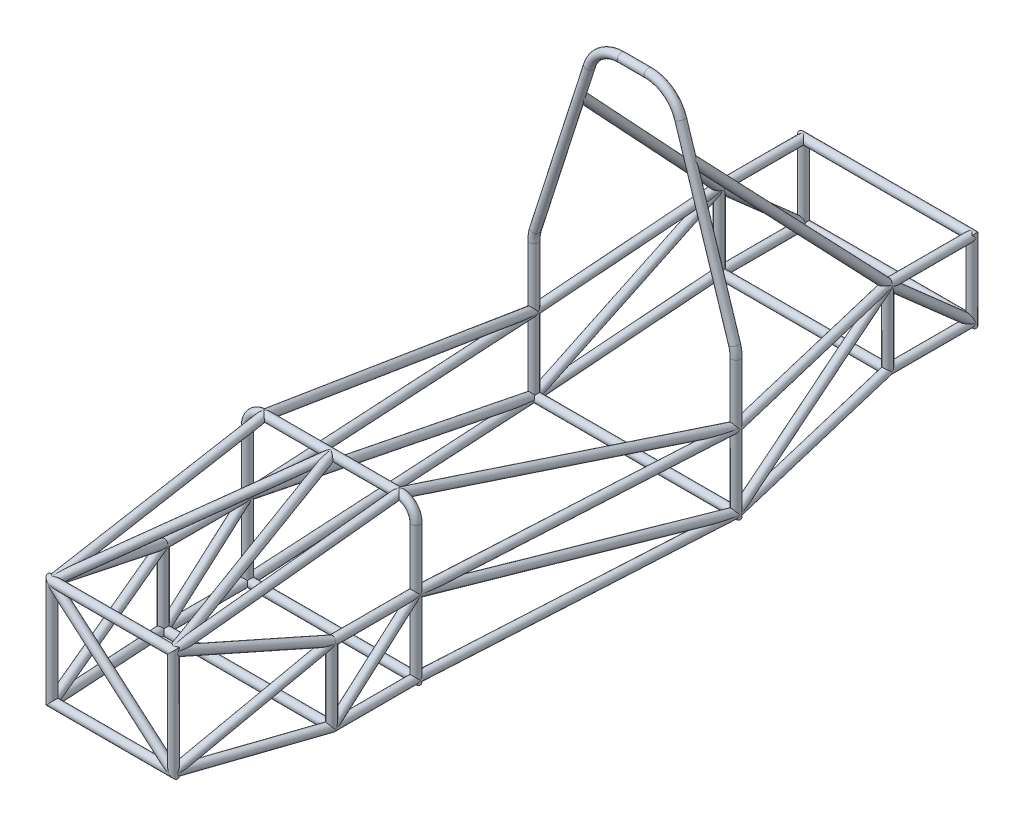
SolidWorks part; units mm, degrees
ref_plane "Front Plane" through (0, 0, 0) normal (0, 0, 1) x (1, 0, 0)
ref_plane "Top Plane" through (0, 0, 0) normal (0, 1, 0) x (1, 0, 0)
ref_plane "Right Plane" through (0, 0, 0) normal (1, 0, 0) x (0, 0, -1)
sketch "Sketch1" plane through (0, 0, 0) normal (0, 0, 1) x (1, 0, 0)
  line L0 (0, 0) -> (0, 400)
  line L1 (4.7576, 430.4776) -> (164.7576, 930.4776)
  line L2 (260, 1000) -> (340, 1000)
  line L3 (435.2424, 930.4776) -> (595.2424, 430.4776)
  line L4 (600, 400) -> (600, 0)
  line L5 (600, 0) -> (0, 0)
  line L6 (300, -975.9464) -> (300, 49024.0536) construction
  arc A0 (595.2424, 430.4776) -> (600, 400) centre (500, 400) cw
  arc A1 (0, 400) -> (4.7576, 430.4776) centre (100, 400) cw
  arc A2 (340, 1000) -> (435.2424, 930.4776) centre (340, 900) cw
  arc A3 (164.7576, 930.4776) -> (260, 1000) centre (260, 900) cw
  dimension "D2" = 100
  dimension "D3" = 100
  dimension "D1" = 600
  dimension "D4" = 300
  dimension "D5" = 400
  dimension "D6" = 80
  dimension "D7" = 1000
sketch "Sketch3" plane through (0, 0, 0) normal (0, 1, 0) x (1, 0, 0)
  line L0 (300, -1107.0637) -> (300, 51069.4933) construction
  dimension "D1" = 300
ref_plane "Plane1" through (0, 0, 900) normal (0, 0, 1) x (1, 0, 0)
sketch "Sketch5" plane through (0, 0, 900) normal (0, 0, 1) x (1, 0, 0)
  line L0 (50, 0) -> (550, 0)
  line L1 (600, 0) -> (0, 0) construction
  line L2 (550, 0) -> (550, 400)
  line L3 (500, 450) -> (100, 450)
  line L4 (50, 400) -> (50, 0)
  arc A0 (550, 400) -> (500, 450) centre (500, 400) ccw
  arc A1 (100, 450) -> (50, 400) centre (100, 400) ccw
  dimension "D1" = 50
  dimension "D2" = 450
  dimension "D3" = 500
  dimension "D4" = 50
sketch3d "3DSketch42"
  line L0 (0, 0, 0) -> (50, 0, 900)
  line L1 (600, 0, 0) -> (550, 0, 900)
sketch3d "3DSketch43"
  line L0 (600, 220, 0) -> (550, 220, 900)
  line L1 (600, 400, 0) -> (600, 0, 0) construction
  line L2 (550, 0, 900) -> (550, 400, 900) construction
  line L3 (550, 220, 900) -> (600, 0, 0)
  line L4 (0, 220, 0) -> (50, 220, 900)
  line L5 (0, 0, 0) -> (0, 400, 0) construction
  line L6 (50, 400, 900) -> (50, 0, 900) construction
  line L7 (50, 220, 900) -> (0, 0, 0)
  dimension "D1" = 220
  dimension "D2" = 220
  dimension "D3" = 220
  dimension "D4" = 220
sketch3d "3DSketch44"
  line L0 (600, 220, 0) -> (500, 450, 900)
  line L1 (0, 220, 0) -> (100, 450, 900)
sketch3d "3DSketch46"
  line L0 (50, 0, 900) -> (50, 0, 1150)
  line L1 (50, 0, 1150) -> (550, 0, 1150)
  line L2 (550, 0, 1150) -> (550, 0, 900)
  dimension "D1" = 250
sketch3d "3DSketch48"
  line L0 (50, 0, 1150) -> (50, 220, 1150)
  line L1 (50, 220, 1150) -> (50, 220, 900)
  line L2 (50, 400, 900) -> (50, 0, 900) construction
  line L3 (50, 0, 1150) -> (50, 220, 900)
  line L4 (550, 0, 1150) -> (550, 220, 1150)
  line L5 (550, 220, 1150) -> (550, 220, 900)
  line L6 (550, 0, 900) -> (550, 400, 900) construction
  line L7 (550, 220, 900) -> (550, 0, 1150)
  dimension "D1" = 220
ref_plane "Plane2" through (0, 0, 1550) normal (0, 0, 1) x (1, 0, 0)
sketch "Sketch6" plane through (0, 0, 1550) normal (0, 0, 1) x (1, 0, 0)
  line L0 (120, 49) -> (480, 49)
  line L1 (480, 49) -> (480, 359)
  line L2 (480, 359) -> (120, 359)
  line L3 (120, 359) -> (120, 49)
  line L4 (0, 0) -> (0, 400) construction
  line L5 (600, 0) -> (0, 0) construction
  dimension "D1" = 360
  dimension "D2" = 310
  dimension "D3" = 120
  dimension "D4" = 49
sketch3d "3DSketch49"
  line L0 (50, 0, 1150) -> (120, 49, 1550)
  line L1 (120, 49, 1550) -> (50, 220, 1150)
  line L2 (50, 220, 1150) -> (120, 359, 1550)
  line L3 (480, 359, 1550) -> (500, 450, 900)
  line L5 (120, 359, 1550) -> (100, 450, 900)
  line L6 (480, 359, 1550) -> (550, 220, 1150)
  line L7 (550, 220, 1150) -> (480, 49, 1550)
  line L8 (480, 49, 1550) -> (480, 359, 1550) construction
  line L9 (120, 49, 1550) -> (480, 49, 1550) construction
  line L10 (480, 49, 1550) -> (550, 0, 1150)
  line L11 (480, 359, 1550) -> (300, 450, 900)
  line L12 (120, 359, 1550) -> (480, 49, 1550)
  line L14 (500, 450, 900) -> (100, 450, 900) construction
  line L15 (300, 450, 900) -> (120, 359, 1550)
ref_plane "Plane3" through (0, 0, -500) normal (0, 0, 1) x (1, 0, 0)
sketch "Sketch7" plane through (0, 0, -500) normal (0, 0, 1) x (1, 0, 0)
  line L0 (50, 92) -> (50, 312)
  line L1 (600, 400) -> (600, 0) construction
  line L2 (550, 312) -> (550, 92)
  line L3 (550, 92) -> (50, 92)
  line L4 (0, 0) -> (0, 400) construction
  line L5 (600, 0) -> (0, 0) construction
  dimension "D1" = 50
  dimension "D2" = 500
  dimension "D3" = 220
  dimension "D4" = 92
sketch3d "3DSketch50"
  line L0 (0, 0, 0) -> (50, 92, -500)
  line L1 (0, 0, 0) -> (50, 312, -500)
  line L2 (50, 312, -500) -> (0, 220, 0)
  line L3 (550, 92, -500) -> (600, 0, 0)
  line L4 (600, 0, 0) -> (550, 312, -500)
  line L5 (550, 312, -500) -> (600, 220, 0)
sketch3d "3DSketch51"
  line L0 (50, 312, -500) -> (135.8048, 840, 0)
  line L1 (4.7576, 430.4776, 0) -> (164.7576, 930.4776, 0) construction
  line L2 (550, 312, -500) -> (464.1952, 840, 0)
  line L3 (435.2424, 930.4776, 0) -> (595.2424, 430.4776, 0) construction
  line L4 (260, 1000, 0) -> (340, 1000, 0) construction
  dimension "D1" = 160
sketch3d "3DSketch52"
  line L0 (550, 92, -500) -> (550, 92, -750)
  line L1 (550, 92, -750) -> (50, 92, -750)
  line L2 (50, 92, -750) -> (50, 92, -500)
  dimension "D1" = 250
sketch3d "3DSketch53"
  line L0 (50, 92, -750) -> (50, 312, -750)
  line L1 (50, 312, -750) -> (550, 312, -750)
  line L2 (550, 312, -750) -> (550, 92, -750)
  dimension "D1" = 220
sketch3d "3DSketch54"
  line L0 (50, 312, -750) -> (50, 312, -500)
  line L1 (50, 312, -500) -> (50, 92, -750)
  line L2 (550, 312, -750) -> (550, 312, -500)
  line L3 (550, 312, -500) -> (550, 92, -750)
other "Pipe MAIN HOOP(1)" corner treatment miter
ref_plane "Plane4" through (600, 400, 0) normal (0, -1, 0) x (1, 0, 0)
sketch "Sketch11" plane through (600, 400, 0) normal (0, -1, 0) x (1, 0, 0)
  circle A0 centre (0, 0) radius 12.7
  circle A1 centre (0, 0) radius 10.3
  point P4 (0, 0)
  dimension "D1" = 25.4
  dimension "D2" = 2.4
other "Pipe MAIN HOOP(2)" corner treatment miter
ref_plane "Plane5" through (550, 0, 900) normal (0, 1, 0) x (-1, 0, 0)
sketch "Sketch12" plane through (550, 0, 900) normal (0, 1, 0) x (-1, 0, 0)
  circle A0 centre (0, 0) radius 12.7
  circle A1 centre (0, 0) radius 10.3
  point P4 (0, 0)
  dimension "D1" = 25.4
  dimension "D2" = 2.4
other "Pipe SECONDARY PROFILE(1)" corner treatment miter
ref_plane "Plane6" through (120, 359, 1550) normal (0, -1, 0) x (1, 0, 0)
sketch "Sketch13" plane through (120, 359, 1550) normal (0, -1, 0) x (1, 0, 0)
  circle A0 centre (0, 0) radius 12.7
  circle A1 centre (0, 0) radius 11.05
  point P4 (0, 0)
  dimension "D1" = 25.4
  dimension "D2" = 1.65
other "Pipe SECONDARY PROFILE(2)" corner treatment miter
ref_plane "Plane7" through (600, 0, 0) normal (-0.0555, 0, 0.9985) x (0.9985, 0, 0.0555)
sketch "Sketch14" plane through (600, 0, 0) normal (-0.0555, 0, 0.9985) x (0.9985, 0, 0.0555)
  circle A0 centre (0, 0) radius 12.7
  circle A1 centre (0, 0) radius 11.05
  point P4 (0, 0)
  dimension "D1" = 25.4
  dimension "D2" = 1.65
other "Pipe SECONDARY PROFILE(3)" corner treatment miter
ref_plane "Plane8" through (550, 220, 900) normal (0.0539, -0.2371, -0.97) x (0.9032, 0.4257, -0.0539)
sketch "Sketch15" plane through (550, 220, 900) normal (0.0539, -0.2371, -0.97) x (0.9032, 0.4257, -0.0539)
  circle A0 centre (0, 0) radius 12.7
  circle A1 centre (0, 0) radius 11.05
  point P4 (0, 0)
  dimension "D1" = 25.4
  dimension "D2" = 1.65
other "Pipe SECONDARY PROFILE(4)" corner treatment miter
ref_plane "Plane9" through (0, 0, 0) normal (0.0555, 0, 0.9985) x (0.9985, 0, -0.0555)
sketch "Sketch16" plane through (0, 0, 0) normal (0.0555, 0, 0.9985) x (0.9985, 0, -0.0555)
  circle A0 centre (0, 0) radius 12.7
  circle A1 centre (0, 0) radius 11.05
  point P4 (0, 0)
  dimension "D1" = 25.4
  dimension "D2" = 1.65
other "Pipe SECONDARY PROFILE(5)" corner treatment miter
ref_plane "Plane10" through (50, 220, 900) normal (-0.0539, -0.2371, -0.97) x (0.9032, -0.4257, 0.0539)
sketch "Sketch17" plane through (50, 220, 900) normal (-0.0539, -0.2371, -0.97) x (0.9032, -0.4257, 0.0539)
  circle A0 centre (0, 0) radius 12.7
  circle A1 centre (0, 0) radius 11.05
  point P4 (0, 0)
  dimension "D1" = 25.4
  dimension "D2" = 1.65
other "Pipe SECONDARY PROFILE(6)" corner treatment miter
ref_plane "Plane11" through (50, 0, 900) normal (0, 0, 1) x (1, 0, 0)
sketch "Sketch18" plane through (50, 0, 900) normal (0, 0, 1) x (1, 0, 0)
  circle A0 centre (0, 0) radius 12.7
  circle A1 centre (0, 0) radius 11.05
  point P4 (0, 0)
  dimension "D1" = 25.4
  dimension "D2" = 1.65
other "Pipe SECONDARY PROFILE(7)" corner treatment miter
ref_plane "Plane12" through (550, 0, 1150) normal (0, 0, -1) x (1, 0, 0)
sketch "Sketch19" plane through (550, 0, 1150) normal (0, 0, -1) x (1, 0, 0)
  circle A0 centre (0, 0) radius 12.7
  circle A1 centre (0, 0) radius 11.05
  point P4 (0, 0)
  dimension "D1" = 25.4
  dimension "D2" = 1.65
other "Pipe SECONDARY PROFILE(8)" corner treatment miter
ref_plane "Plane13" through (50, 0, 1150) normal (1, 0, 0) x (0, 0, -1)
sketch "Sketch110" plane through (50, 0, 1150) normal (1, 0, 0) x (0, 0, -1)
  circle A0 centre (0, 0) radius 12.7
  circle A1 centre (0, 0) radius 11.05
  point P4 (0, 0)
  dimension "D1" = 25.4
  dimension "D2" = 1.65
other "Pipe SECONDARY PROFILE(9)" corner treatment miter
ref_plane "Plane14" through (120, 359, 1550) normal (0.7578, -0.6525, 0) x (0.4258, 0.4945, -0.7578)
sketch "Sketch111" plane through (120, 359, 1550) normal (0.7578, -0.6525, 0) x (0.4258, 0.4945, -0.7578)
  circle A0 centre (0, 0) radius 12.7
  circle A1 centre (0, 0) radius 11.05
  point P4 (0, 0)
  dimension "D1" = 25.4
  dimension "D2" = 1.65
other "Pipe SECONDARY PROFILE(10)" corner treatment miter
ref_plane "Plane15" through (120, 359, 1550) normal (-0.0305, 0.1386, -0.9899) x (0.9083, 0.4172, 0.0305)
sketch "Sketch112" plane through (120, 359, 1550) normal (-0.0305, 0.1386, -0.9899) x (0.9083, 0.4172, 0.0305)
  circle A0 centre (0, 0) radius 12.7
  circle A1 centre (0, 0) radius 11.05
  point P4 (0, 0)
  dimension "D1" = 25.4
  dimension "D2" = 1.65
other "Pipe SECONDARY PROFILE(11)" corner treatment miter
ref_plane "Plane16" through (480, 359, 1550) normal (0.0305, 0.1386, -0.9899) x (0.9083, -0.4172, -0.0305)
sketch "Sketch113" plane through (480, 359, 1550) normal (0.0305, 0.1386, -0.9899) x (0.9083, -0.4172, -0.0305)
  circle A0 centre (0, 0) radius 12.7
  circle A1 centre (0, 0) radius 11.05
  point P4 (0, 0)
  dimension "D1" = 25.4
  dimension "D2" = 1.65
other "Pipe SECONDARY PROFILE(12)"
ref_plane "Plane17" through (300, 450, 900) normal (-0.2645, -0.1337, 0.9551) x (0.9642, -0.0181, 0.2645)
sketch "Sketch114" plane through (300, 450, 900) normal (-0.2645, -0.1337, 0.9551) x (0.9642, -0.0181, 0.2645)
  circle A0 centre (0, 0) radius 12.7
  circle A1 centre (0, 0) radius 11.05
  point P4 (0, 0)
  dimension "D1" = 25.4
  dimension "D2" = 1.65
other "Pipe SECONDARY PROFILE(14)" corner treatment miter
ref_plane "Plane21" through (550, 92, -750) normal (-1, 0, 0) x (0, 0, 1)
sketch "Sketch118" plane through (550, 92, -750) normal (-1, 0, 0) x (0, 0, 1)
  circle A0 centre (0, 0) radius 12.7
  circle A1 centre (0, 0) radius 11.05
  point P4 (0, 0)
  dimension "D1" = 25.4
  dimension "D2" = 1.65
other "Pipe SECONDARY PROFILE(16)" corner treatment miter
ref_plane "Plane24" through (550, 220, 1150) normal (0, 0, -1) x (1, 0, 0)
sketch "Sketch121" plane through (550, 220, 1150) normal (0, 0, -1) x (1, 0, 0)
  circle A0 centre (0, 0) radius 12.7
  circle A1 centre (0, 0) radius 11.05
  point P4 (0, 0)
  dimension "D1" = 25.4
  dimension "D2" = 1.65
other "Pipe SECONDARY PROFILE(17)" corner treatment miter
ref_plane "Plane25" through (50, 220, 1150) normal (0, 0, -1) x (1, 0, 0)
sketch "Sketch122" plane through (50, 220, 1150) normal (0, 0, -1) x (1, 0, 0)
  circle A0 centre (0, 0) radius 12.7
  circle A1 centre (0, 0) radius 11.05
  point P4 (0, 0)
  dimension "D1" = 25.4
  dimension "D2" = 1.65
other "Pipe SECONDARY PROFILE(18)" corner treatment miter
ref_plane "Plane26" through (50, 0, 1150) normal (0, 1, 0) x (1, 0, 0)
sketch "Sketch123" plane through (50, 0, 1150) normal (0, 1, 0) x (1, 0, 0)
  circle A0 centre (0, 0) radius 12.7
  circle A1 centre (0, 0) radius 11.05
  point P4 (0, 0)
  dimension "D1" = 25.4
  dimension "D2" = 1.65
other "Pipe SECONDARY PROFILE(19)" corner treatment miter
ref_plane "Plane27" through (550, 0, 1150) normal (0, 1, 0) x (1, 0, 0)
sketch "Sketch124" plane through (550, 0, 1150) normal (0, 1, 0) x (1, 0, 0)
  circle A0 centre (0, 0) radius 12.7
  circle A1 centre (0, 0) radius 11.05
  point P4 (0, 0)
  dimension "D1" = 25.4
  dimension "D2" = 1.65
other "Pipe SECONDARY PROFILE(20)" corner treatment miter
ref_plane "Plane28" through (50, 0, 1150) normal (0, 0.6606, -0.7507) x (1, 0, 0)
sketch "Sketch125" plane through (50, 0, 1150) normal (0, 0.6606, -0.7507) x (1, 0, 0)
  circle A0 centre (0, 0) radius 12.7
  circle A1 centre (0, 0) radius 11.05
  point P4 (0, 0)
  dimension "D1" = 25.4
  dimension "D2" = 1.65
other "Pipe SECONDARY PROFILE(21)" corner treatment miter
ref_plane "Plane29" through (550, 220, 900) normal (0, -0.6606, 0.7507) x (1, 0, 0)
sketch "Sketch126" plane through (550, 220, 900) normal (0, -0.6606, 0.7507) x (1, 0, 0)
  circle A0 centre (0, 0) radius 12.7
  circle A1 centre (0, 0) radius 11.05
  point P4 (0, 0)
  dimension "D1" = 25.4
  dimension "D2" = 1.65
other "Pipe SECONDARY PROFILE(22)" corner treatment miter
ref_plane "Plane30" through (120, 49, 1550) normal (-0.1589, 0.3881, -0.9078) x (0.7262, 0.6689, 0.1589)
sketch "Sketch127" plane through (120, 49, 1550) normal (-0.1589, 0.3881, -0.9078) x (0.7262, 0.6689, 0.1589)
  circle A0 centre (0, 0) radius 12.7
  circle A1 centre (0, 0) radius 11.05
  point P4 (0, 0)
  dimension "D1" = 25.4
  dimension "D2" = 1.65
other "Pipe SECONDARY PROFILE(23)" corner treatment miter
ref_plane "Plane31" through (550, 220, 1150) normal (-0.1589, -0.3881, 0.9078) x (0.9868, -0.0323, 0.1589)
sketch "Sketch128" plane through (550, 220, 1150) normal (-0.1589, -0.3881, 0.9078) x (0.9868, -0.0323, 0.1589)
  circle A0 centre (0, 0) radius 12.7
  circle A1 centre (0, 0) radius 11.05
  point P4 (0, 0)
  dimension "D1" = 25.4
  dimension "D2" = 1.65
other "Pipe SECONDARY PROFILE(24)" corner treatment miter
ref_plane "Plane32" through (550, 92, -500) normal (0.0979, -0.1801, 0.9788) x (0.9952, 0.0089, -0.0979)
sketch "Sketch129" plane through (550, 92, -500) normal (0.0979, -0.1801, 0.9788) x (0.9952, 0.0089, -0.0979)
  circle A0 centre (0, 0) radius 12.7
  circle A1 centre (0, 0) radius 11.05
  point P4 (0, 0)
  dimension "D1" = 25.4
  dimension "D2" = 1.65
other "Pipe SECONDARY PROFILE(25)" corner treatment miter
ref_plane "Plane33" through (0, 0, 0) normal (0.0979, 0.1801, -0.9788) x (0.5488, -0.8302, -0.0979)
sketch "Sketch130" plane through (0, 0, 0) normal (0.0979, 0.1801, -0.9788) x (0.5488, -0.8302, -0.0979)
  circle A0 centre (0, 0) radius 12.7
  circle A1 centre (0, 0) radius 11.05
  point P4 (0, 0)
  dimension "D1" = 25.4
  dimension "D2" = 1.65
other "Pipe SECONDARY PROFILE(26)" corner treatment miter
ref_plane "Plane34" through (550, 312, -500) normal (0.0979, -0.1801, 0.9788) x (0.9952, 0.0089, -0.0979)
sketch "Sketch131" plane through (550, 312, -500) normal (0.0979, -0.1801, 0.9788) x (0.9952, 0.0089, -0.0979)
  circle A0 centre (0, 0) radius 12.7
  circle A1 centre (0, 0) radius 11.05
  point P4 (0, 0)
  dimension "D1" = 25.4
  dimension "D2" = 1.65
other "Pipe SECONDARY PROFILE(27)" corner treatment miter
ref_plane "Plane35" through (50, 312, -500) normal (-0.0979, -0.1801, 0.9788) x (0.9952, -0.0089, 0.0979)
sketch "Sketch132" plane through (50, 312, -500) normal (-0.0979, -0.1801, 0.9788) x (0.9952, -0.0089, 0.0979)
  circle A0 centre (0, 0) radius 12.7
  circle A1 centre (0, 0) radius 11.05
  point P4 (0, 0)
  dimension "D1" = 25.4
  dimension "D2" = 1.65
other "Pipe SECONDARY PROFILE(28)" corner treatment miter
ref_plane "Plane36" through (550, 312, -500) normal (0, -1, 0) x (1, 0, 0)
sketch "Sketch133" plane through (550, 312, -500) normal (0, -1, 0) x (1, 0, 0)
  circle A0 centre (0, 0) radius 12.7
  circle A1 centre (0, 0) radius 11.05
  point P4 (0, 0)
  dimension "D1" = 25.4
  dimension "D2" = 1.65
other "Pipe SECONDARY PROFILE(29)" corner treatment miter
ref_plane "Plane37" through (50, 92, -500) normal (0, 1, 0) x (-1, 0, 0)
sketch "Sketch134" plane through (50, 92, -500) normal (0, 1, 0) x (-1, 0, 0)
  circle A0 centre (0, 0) radius 12.7
  circle A1 centre (0, 0) radius 11.05
  point P4 (0, 0)
  dimension "D1" = 25.4
  dimension "D2" = 1.65
other "Pipe SECONDARY PROFILE(30)" corner treatment miter
ref_plane "Plane38" through (550, 92, -500) normal (-1, 0, 0) x (0, -1, 0)
sketch "Sketch135" plane through (550, 92, -500) normal (-1, 0, 0) x (0, -1, 0)
  circle A0 centre (0, 0) radius 12.7
  circle A1 centre (0, 0) radius 11.05
  point P4 (0, 0)
  dimension "D1" = 25.4
  dimension "D2" = 1.65
other "Pipe SECONDARY PROFILE(32)" corner treatment miter
ref_plane "Plane40" through (600, 0, 0) normal (-0.0845, 0.5275, -0.8453) x (0.9538, 0.2883, 0.0845)
sketch "Sketch137" plane through (600, 0, 0) normal (-0.0845, 0.5275, -0.8453) x (0.9538, 0.2883, 0.0845)
  circle A0 centre (0, 0) radius 12.7
  circle A1 centre (0, 0) radius 11.05
  point P4 (0, 0)
  dimension "D1" = 25.4
  dimension "D2" = 1.65
other "Pipe SECONDARY PROFILE(33)" corner treatment miter
ref_plane "Plane41" through (0, 0, 0) normal (0.0845, 0.5275, -0.8453) x (0.9538, -0.2883, -0.0845)
sketch "Sketch138" plane through (0, 0, 0) normal (0.0845, 0.5275, -0.8453) x (0.9538, -0.2883, -0.0845)
  circle A0 centre (0, 0) radius 12.7
  circle A1 centre (0, 0) radius 11.05
  point P4 (0, 0)
  dimension "D1" = 25.4
  dimension "D2" = 1.65
other "Pipe SECONDARY PROFILE(34)" corner treatment miter
ref_plane "Plane42" through (50, 312, -500) normal (0, -0.6606, -0.7507) x (1, 0, 0)
sketch "Sketch139" plane through (50, 312, -500) normal (0, -0.6606, -0.7507) x (1, 0, 0)
  circle A0 centre (0, 0) radius 12.7
  circle A1 centre (0, 0) radius 11.05
  point P4 (0, 0)
  dimension "D1" = 25.4
  dimension "D2" = 1.65
other "Pipe SECONDARY PROFILE(35)" corner treatment miter
ref_plane "Plane43" through (550, 312, -500) normal (0, -0.6606, -0.7507) x (1, 0, 0)
sketch "Sketch140" plane through (550, 312, -500) normal (0, -0.6606, -0.7507) x (1, 0, 0)
  circle A0 centre (0, 0) radius 12.7
  circle A1 centre (0, 0) radius 11.05
  point P4 (0, 0)
  dimension "D1" = 25.4
  dimension "D2" = 1.65
